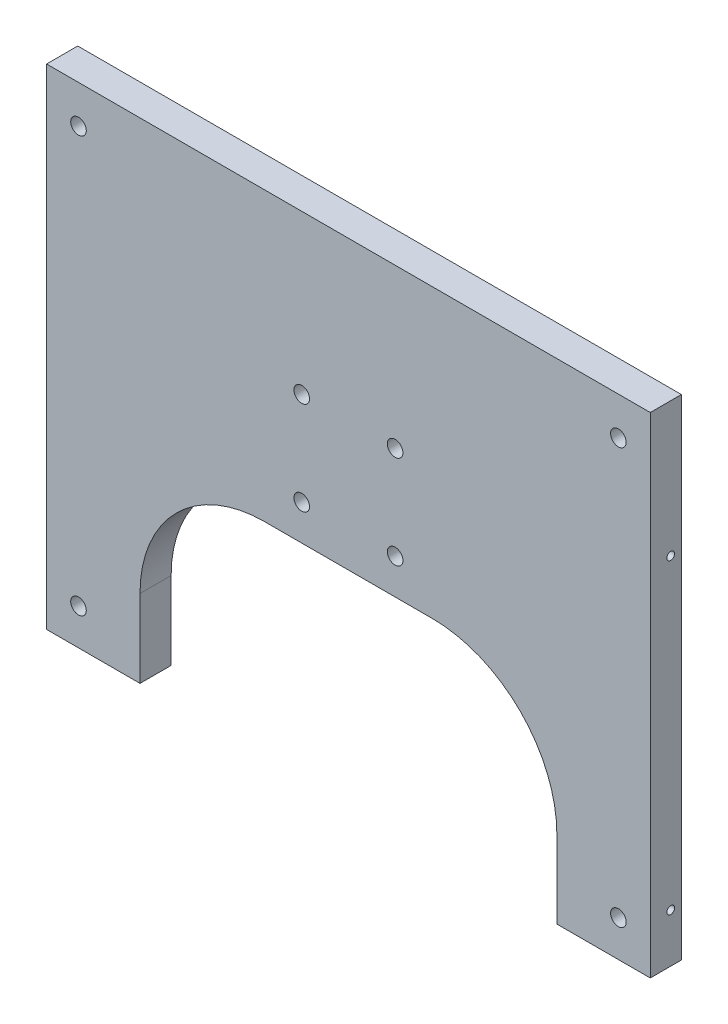
SolidWorks part; units mm, degrees
material "Beech"
ref_plane "Front Plane" through (0, 0, 0) normal (0, 0, 1) x (1, 0, 0)
ref_plane "Top Plane" through (0, 0, 0) normal (0, 1, 0) x (1, 0, 0)
ref_plane "Right Plane" through (0, 0, 0) normal (1, 0, 0) x (0, 0, -1)
sketch "Sketch1" plane through (0, 0, 0) normal (0, 0, 1) x (1, 0, 0)
  line L0 (258.9335, 10.7139) -> (12.7, 10.7139)
  line L1 (135.8167, -73.0143) -> (135.8167, 40.1583) construction
  line L2 (12.7, 10.7139) -> (12.7, -189.0518)
  line L3 (12.7, -189.0518) -> (50.8, -189.0518)
  line L4 (50.8, -189.0518) -> (50.8, -106.5018)
  line L5 (50.8, -106.5018) -> (220.8335, -106.5018)
  line L6 (135.8167, -205.9834) -> (135.8167, -73.0143) construction
  line L7 (135.8167, -106.5018) -> (135.8167, 10.7139) construction
  line L8 (271.3655, 10.7139) -> (0, 10.7139) construction
  line L9 (12.7, -189.0518) -> (12.7, 10.2705) construction
  line L10 (220.8335, -189.0518) -> (220.8335, -106.5018)
  line L11 (258.9335, -189.0518) -> (220.8335, -189.0518)
  line L12 (258.9335, 10.7139) -> (258.9335, -189.0518)
  dimension "D1" = 38.1
  dimension "D2" = 82.55
extrude "Boss-Extrude1" add sketch "Sketch1" against normal blind 12.7
hole_wizard "1/4 (0.25) Diameter Hole1" positions "Sketch4" profile "Sketch5" hole size "1/4" standard "ANSI Inch" end condition through all
sketch "Sketch4" plane through (0, 0, -12.7) normal (0, 0, -1) x (-1, 0, 0)
  point P0 (-25.7062, -174.2334)
  point P6 (-116.7667, -92.0643)
  point P9 (-154.8667, -92.0643)
  point P12 (-245.9273, -174.2334)
  point P15 (-154.8667, -53.9643)
  point P18 (-245.9273, -4.748)
  point P21 (-116.7667, -53.9643)
  point P24 (-25.7062, -4.748)
sketch "Sketch5" plane through (25.7062, -174.2334, -12.7) normal (1, 0, 0) x (0, 1, 0)
  line L0 (0, 0) -> (0, 12.7)
  line L1 (0, 12.7) -> (3.175, 12.7)
  line L2 (3.175, 12.7) -> (3.175, 0)
  line L5 (3.175, 0) -> (0, 0)
  line L11 (0, -6.35) -> (0, 107.95) construction
  dimension "Thru Hole Dia." = 6.35
  dimension "Thru Hole Depth" = 12.7
fillet "Fillet2" radius 50.8 2 edges at (220.8335, -106.5018, -6.35) (50.8, -106.5018, -6.35)
hole_wizard "Hole1" positions "Sketch6" profile "Sketch7" legacy
sketch "Sketch6" plane through (0, 1044.977, 392.3998) normal (-1, 0, 0) x (0, -0.2641, -0.9645)
  point P29 (707.1666, 1065.2704)
  point P31 (674.128, 944.6031)
sketch "Sketch7" plane through (0, -169.2253, -8.3471) normal (0, 1, 0) x (0, 0, 1)
  line L0 (0, 0) -> (0, 39.0539)
  line L1 (0, 39.0539) -> (1.5875, 38.1)
  line L2 (1.5875, 38.1) -> (1.5875, 4.0177)
  line L3 (1.5875, 4.0177) -> (5.08, 0)
  line L4 (5.08, 0) -> (0, 0)
  line L5 (0, -14.3089) -> (0, 102.4216) construction
  line L6 (0, 39.0539) -> (-1.5875, 38.1) construction
  line L7 (-1.5875, 4.0177) -> (-5.08, 0) construction
  dimension "Diameter" = 3.175
  dimension "Depth" = 38.1
  dimension "C-Sink Diameter" = 10.16
  dimension "C-Sink Angle" = 82
  dimension "Drill Angle" = 118
ref_plane "Plane1" through (135.8167, 0, 0) normal (-1, 0, 0) x (0, 0, 1)
mirror "Mirror1" about plane through (135.8167, 0, 0) normal (-1, 0, 0) of "Hole1"
